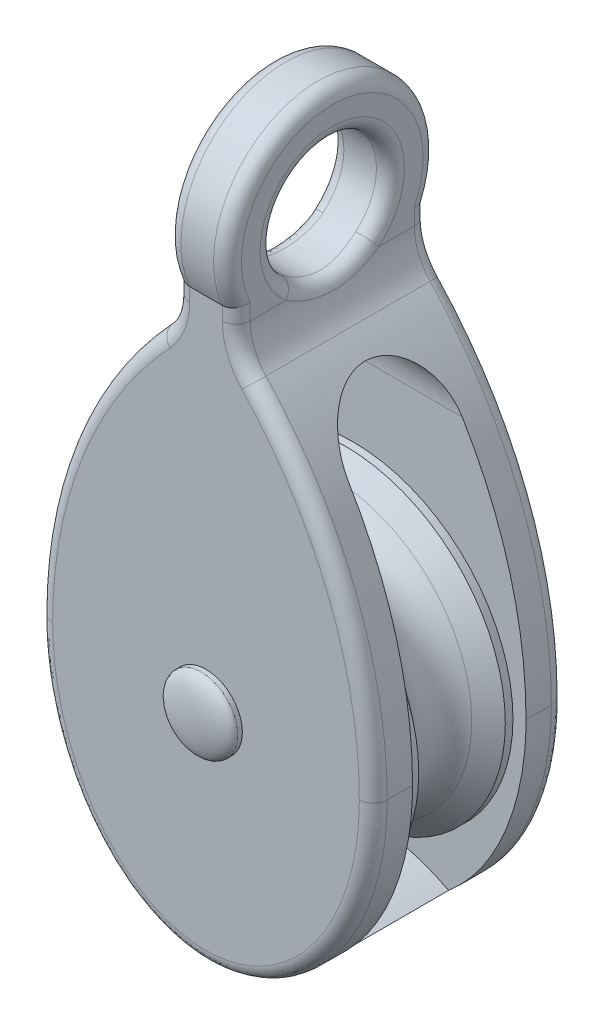
SolidWorks part; units mm, degrees
ref_plane "Front Plane" through (0, 0, 0) normal (0, 0, 1) x (1, 0, 0)
ref_plane "Top Plane" through (0, 0, 0) normal (0, 1, 0) x (1, 0, 0)
ref_plane "Right Plane" through (0, 0, 0) normal (1, 0, 0) x (0, 0, -1)
sketch "Sketch1" plane through (0, 0, 0) normal (1, 0, 0) x (0, 0, -1)
  line L0 (-4.7228, 17.4625) -> (-3.0831, 15.4396)
  line L1 (-5.5562, 17.4625) -> (-4.7228, 17.4625)
  line L2 (-5.5562, 17.4625) -> (-5.5562, 0)
  line L3 (-5.5562, 0) -> (-9.2704, 0) construction
  line L4 (5.5562, 17.4625) -> (5.5562, 0)
  line L5 (3.0831, 15.4396) -> (4.7228, 17.4625)
  line L6 (4.7228, 17.4625) -> (5.5562, 17.4625)
  line L7 (5.5562, 0) -> (-5.5562, 0) construction
  line L8 (-5.5562, 0) -> (5.5562, 0)
  arc A0 (-3.0831, 15.4396) -> (3.0831, 15.4396) centre (0, 17.9388) ccw
  circle A1 centre (0, 17.9388) radius 3.9688 construction
  circle A2 centre (0, -17.9388) radius 3.9688 construction
  dimension "D3" = 0.8334
  dimension "Rope Dia" = 7.9375
  dimension "D2" = 27.94
  dimension "pulley width" = 11.1125
  dimension "Pulley OD" = 34.925
revolve "Revolve1" add sketch "Sketch1" angle 360 about L3
sketch "Sketch2" plane through (0, 0, 0) normal (0, 0, 1) x (1, 0, 0)
  line L0 (0, 37.465) -> (0, -24.13) construction
  line L1 (-18.2562, 0) -> (18.2562, 0) construction
  line L9 (-3.302, 35.179) -> (3.302, 35.179) construction
  line L10 (-3.302, 55.245) -> (3.302, 55.245)
  line L11 (-3.302, 55.245) -> (-3.302, 35.179)
  line L12 (3.302, 35.179) -> (3.302, 55.245)
  arc A0 (18.2562, 0) -> (3.302, 35.179) centre (-30.5991, 0) ccw
  arc A1 (-3.302, 35.179) -> (-18.2562, 0) centre (30.5991, 0) ccw
  circle A2 centre (0, 0) radius 17.4625 construction
  circle A3 centre (0, 0) radius 17.4625
  circle A4 centre (0, 43.815) radius 6.35
  ellipse E0 centre (0, 0) end of major axis (0, -24.13) minor radius 18.2562
  point P2 (0, 35.179)
  point P27 (0, 55.245)
  point P28 (0, 50.165)
  dimension "opening" = 12.7
  dimension "D1" = 6.604
  dimension "D2" = 20.066
  dimension "Center to base" = 24.13
  dimension "Height" = 79.375
  dimension "width" = 36.5125
  dimension "swivel Dia" = 5.08
sketch "Sketch3" plane through (0, 0, 0) normal (0, 0, 1) x (1, 0, 0)
  line L0 (-3.302, 35.179) -> (3.302, 35.179) construction
  line L1 (-3.302, 55.245) -> (3.302, 55.245) construction
  line L2 (-3.302, 55.245) -> (-3.302, 35.179) construction
  line L3 (3.302, 35.179) -> (3.302, 55.245) construction
  line L4 (-3.302, 55.245) -> (3.302, 55.245)
  line L5 (-3.302, 55.245) -> (-3.302, 37.782)
  line L6 (3.302, 37.782) -> (3.302, 55.245)
  arc A0 (-3.302, 35.179) -> (-18.2562, 0) centre (30.5991, 0) ccw construction
  arc A1 (18.2562, 0) -> (3.302, 35.179) centre (-30.5991, 0) ccw construction
  arc A2 (-5.0221, 33.4361) -> (-18.2562, 0) centre (30.5991, 0) ccw
  arc A3 (18.2562, 0) -> (5.0221, 33.4361) centre (-30.5991, 0) ccw
  arc A4 (5.0221, 33.4361) -> (3.302, 37.782) centre (9.652, 37.782) cw
  arc A5 (-5.0221, 33.4361) -> (-3.302, 37.782) centre (-9.652, 37.782) ccw
  ellipse E0 centre (0, 0) end of major axis (0, -24.13) minor radius 18.2562 construction
  ellipse E1 centre (0, 0) end of major axis (0, -24.13) minor radius 18.2562 (-18.2562, 0) -> (18.2562, 0) ccw
  dimension "D1" = 6.35
extrude "Boss-Extrude1" add sketch "Sketch3" along normal mid plane 20.955 separate body
sketch "Sketch4" plane through (0, 0, 0) normal (1, 0, 0) x (0, 0, -1)
  line L0 (0, 0) -> (0, 25.1301) construction
  line L1 (-6.1913, 25.1301) -> (6.1913, 25.1301) construction
  line L2 (-6.1913, 25.1301) -> (-6.1913, -17.9388)
  line L3 (-6.1913, -17.9388) -> (6.1913, -17.9388)
  line L4 (6.1913, 25.1301) -> (6.1913, -17.9388)
  line L5 (-10.4775, 35.179) -> (10.4775, 35.179) construction
  line L8 (5.5562, 17.4625) -> (5.5562, 0) construction
  line L9 (6.1913, 25.1301) -> (10.4775, 25.1301) construction
  line L10 (10.4775, 0) -> (10.4775, 33.4361) construction
  line L11 (0, 35.179) -> (0, 31.3214) construction
  arc A0 (-6.1913, 25.1301) -> (6.1913, 25.1301) centre (0, 25.1301) cw
  circle A1 centre (0, 43.815) radius 6.35
  dimension "D1" = 0.635
  dimension "D3" = 4.2862
  dimension "D4" = 3.8576
extrude "Cut-Extrude1" cut sketch "Sketch4" against normal blind 76.2 and the other way blind 76.2
sketch "Sketch20" plane through (0, 0, 0) normal (1, 0, 0) x (0, 0, -1)
  circle A0 centre (0, 43.815) radius 11.43
  circle A1 centre (0, 43.815) radius 6.35 construction
  circle A2 centre (0, 43.815) radius 6.35
extrude "Boss-Extrude5" add sketch "Sketch20" along normal up to vertex (3.302 mm away) and the other way up to vertex (3.302 mm away) up to point (3.302, 55.245, 0) other way up to point (-3.302, 55.245, 0)
sketch "Sketch21" plane through (-3.302, 0, 0) normal (-1, 0, 0) x (0, 0, 1)
  line L0 (-11.43, 43.815) -> (-13.97, 43.815)
  line L1 (-13.97, 43.815) -> (-13.97, 57.785)
  line L2 (-13.97, 57.785) -> (13.97, 57.785)
  line L3 (13.97, 57.785) -> (13.97, 43.815)
  line L4 (11.43, 43.815) -> (13.97, 43.815)
  line L5 (10.4775, 55.245) -> (-10.4775, 55.245) construction
  arc A0 (11.43, 43.815) -> (-11.43, 43.815) centre (0, 43.815) ccw
  dimension "D1" = 2.54
  dimension "D2" = 2.54
extrude "Cut-Extrude3" cut sketch "Sketch21" against normal through all
sketch "Sketch6" plane through (0, 0, 0) normal (0, 0, 1) x (1, 0, 0)
  line L0 (0, 37.465) -> (0, -24.13) construction
  line L1 (-12.2102, -17.9388) -> (12.2102, -17.9388) construction
  line L4 (-12.2102, -16.6688) -> (12.2102, -16.6688)
  line L5 (-13.2003, -16.6688) -> (13.2003, -16.6687)
  arc A0 (-9.8082, -20.3517) -> (9.8082, -20.3517) centre (0, -39.0792) cw
  ellipse E0 centre (0, 0) end of major axis (0, -24.13) minor radius 18.2562 construction
  ellipse E1 centre (0, 0) end of major axis (0, -24.13) minor radius 18.2562 (-13.2003, -16.6688) -> (-9.8082, -20.3517) ccw
  ellipse E2 centre (0, 0) end of major axis (0, -24.13) minor radius 18.2562 (9.8082, -20.3517) -> (13.2003, -16.6687) ccw
  dimension "D2" = 3.683
  dimension "D1" = 1.27
extrude "Cut-Extrude2" cut sketch "Sketch6" against normal up to surface and the other way up to surface up to face at (0, 2.2715, -6.1913) other way up to face at (0, 2.2715, 6.1913)
fillet "Fillet2" radius 1.524 20 edges at (-14.8274, 17.98, -10.4775) (0, -24.13, -10.4775) (-14.8274, 17.98, 10.4775) (0, -24.13, 10.4775) (14.8274, 17.98, -10.4775) (14.8274, 17.98, 10.4775) (-3.302, 38.5145, -10.4775) (3.302, 38.5145, 10.4775) (3.302, 38.5145, -10.4775) (-3.302, 38.5145, 10.4775) (-3.302, 55.245, 0) (3.302, 55.245, 0) (-3.7477, 35.4451, -10.4775) (3.7477, 35.4451, -10.4775) (-3.7477, 35.4451, 10.4775) (3.7477, 35.4451, 10.4775)
sketch "Sketch7" plane through (0, 0, -10.4775) normal (0, 0, -1) x (-1, 0, 0)
  circle A0 centre (0, 0) radius 3.9688
  dimension "D1" = 7.9375
extrude "Boss-Extrude2" add sketch "Sketch7" along normal blind 0.508
dome "Dome1" faces to dome 1 distance 1.27 reverse direction no elliptical dome yes face at (-3.9688, 0, -10.9855) parameters "D1"=1.27
mirror "Mirror1" about plane through (0, 0, 0) normal (0, 0, 1) of "Boss-Extrude2", "Dome1"
sketch "Sketch8" plane through (0, 0, -6.1913) normal (0, 0, 1) x (1, 0, 0)
  circle A0 centre (0, 0) radius 2.3812
  dimension "D1" = 4.7625
extrude "Boss-Extrude3" add sketch "Sketch8" along normal up to surface (12.3825 mm away) up to face at (0, 1.6756, 6.1913)
equation "\"D3@Sketch1\" = \"pulley width@Sketch1\"*.075"
equation "\"D2@Sketch1\" = \"Pulley OD@Sketch1\"*.80"
equation "\"D4@Sketch4\" = \"D3@Sketch4\"*.9"
